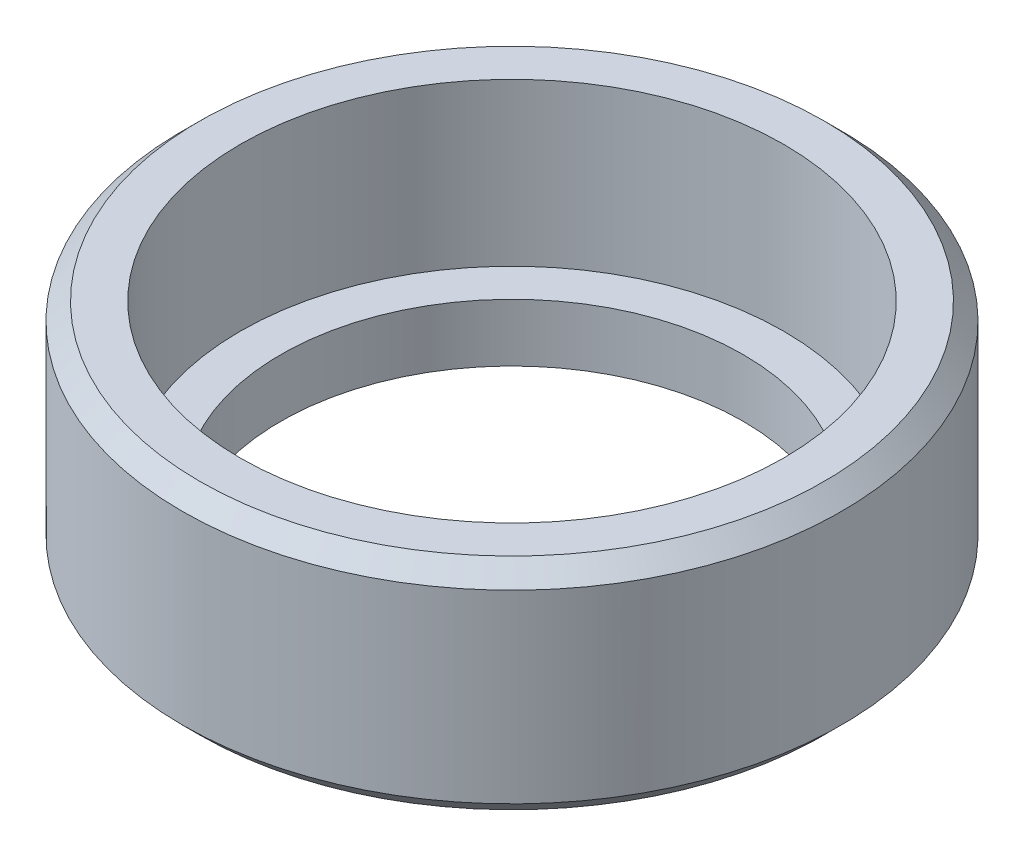
SolidWorks part; units mm, degrees
material "Сталь 3 ГОСТ 535-88"
ref_plane "Спереди" through (0, 0, 0) normal (0, 0, 1) x (1, 0, 0)
ref_plane "Сверху" through (0, 0, 0) normal (0, 1, 0) x (1, 0, 0)
ref_plane "Справа" through (0, 0, 0) normal (1, 0, 0) x (0, 0, -1)
sketch "Эскиз1" plane through (0, 0, 0) normal (1, 0, 0) x (0, 0, -1)
  line L0 (0, 19.7712) -> (0, -17.6113) construction
  line L1 (-20, 5) -> (-20, 0)
  line L2 (-20, 0) -> (-28.5, 0)
  line L3 (-28.5, 0) -> (-28.5, 19)
  line L4 (-28.5, 19) -> (-23.5, 19)
  line L5 (-23.5, 19) -> (-23.5, 5)
  line L6 (-23.5, 5) -> (-20, 5)
  dimension "D1" = 57
  dimension "D2" = 47
  dimension "D3" = 40
  dimension "D4" = 19
  dimension "D5" = 14
revolve "Повернуть1" add sketch "Эскиз1" angle 360 about L0
chamfer "Фаска1" distance 1.5 angle 45 2 edges at (0, 19, 28.5) (0, 0, 28.5)
